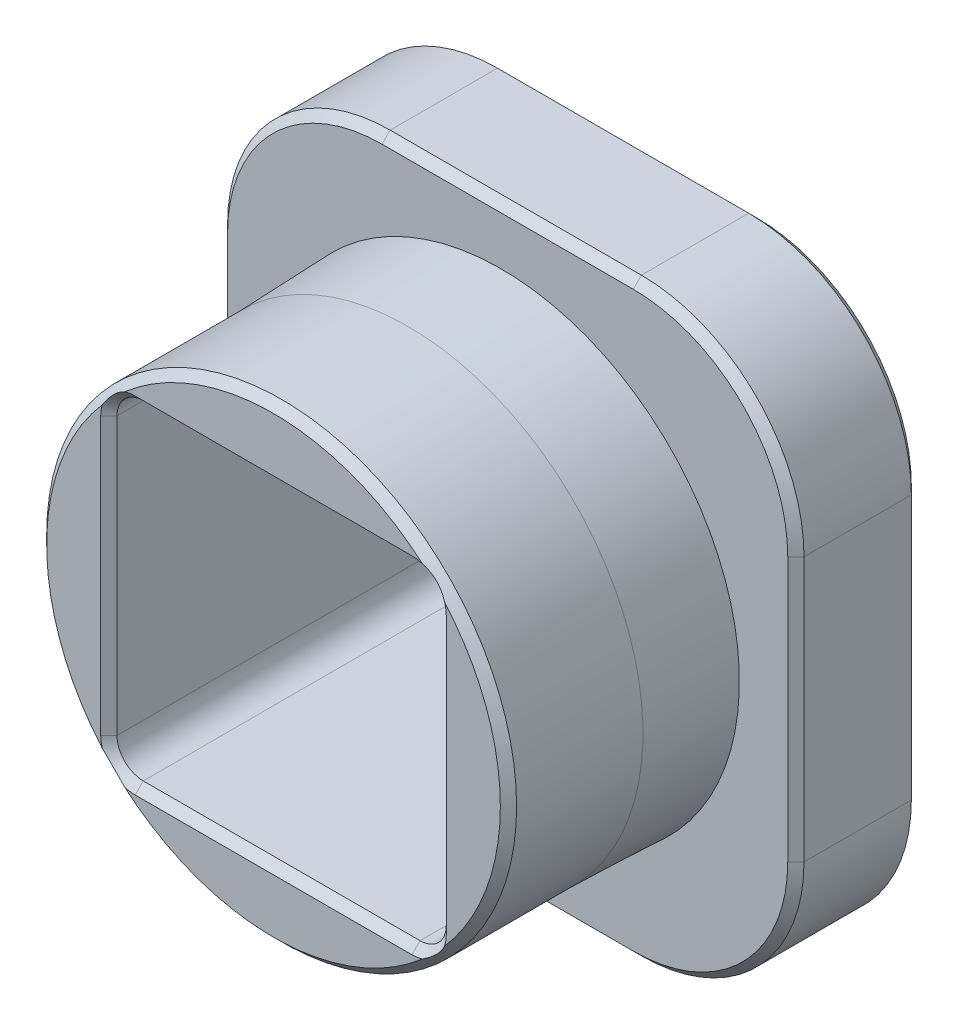
SolidWorks part; units mm, degrees
ref_plane "Front Plane (Z)" through (0, 0, 0) normal (0, 0, 1) x (1, 0, 0)
ref_plane "Top Plane (Y)" through (0, 0, 0) normal (0, 1, 0) x (1, 0, 0)
ref_plane "Side Plane (X)" through (0, 0, 0) normal (1, 0, 0) x (0, 0, -1)
sketch "Sketch1" plane through (0, 0, 0) normal (0, 0, 1) x (1, 0, 0)
  line L0 (9.652, -9.652) -> (10.3465, -8.9575) construction
  line L1 (-8.5101, -10.125) -> (8.5101, -10.125)
  line L2 (-10.125, -8.5101) -> (-10.125, 8.5101)
  line L3 (-8.5101, 10.125) -> (8.5101, 10.125)
  line L4 (10.125, -8.5101) -> (10.125, 8.5101)
  line L5 (-10.125, -10.125) -> (10.125, 10.125) construction
  line L6 (-10.125, 10.125) -> (10.125, -10.125) construction
  line L7 (-9.652, 9.652) -> (-9.1112, 10.1928) construction
  circle A0 centre (0, 0) radius 14.45
  arc A1 (8.5101, -10.125) -> (10.125, -8.5101) centre (8.5101, -8.5101) ccw
  arc A2 (-8.5101, 10.125) -> (-10.125, 8.5101) centre (-8.5101, 8.5101) ccw
  arc A3 (-8.5101, -10.125) -> (-10.125, -8.5101) centre (-8.5101, -8.5101) cw
  arc A4 (10.125, 8.5101) -> (8.5101, 10.125) centre (8.5101, 8.5101) ccw
  point P0 (0, 0)
  dimension "D2" = 28.9
  dimension "D3" = 27.3
  dimension "D1" = 20.25
extrude "Boss-Extrude1" add sketch "Sketch1" along normal blind 14
sketch "Sketch2" plane through (0, 0, 0) normal (0, 0, -1) x (-1, 0, 0)
  line L0 (10.125, 8.5101) -> (10.125, -8.5101) construction
  line L1 (-18.125, -18.125) -> (17.325, -18.125)
  line L2 (-18.125, -18.125) -> (-18.125, 18.125)
  line L3 (-18.125, 18.125) -> (17.325, 18.125)
  line L4 (18.125, -18.125) -> (18.125, 18.125) construction
  line L5 (-18.125, -18.125) -> (18.125, 18.125) construction
  line L6 (-18.125, 18.125) -> (18.125, -18.125) construction
  line L8 (17.325, 18.125) -> (17.325, -18.125)
  line L10 (8.5101, -10.125) -> (-8.5101, -10.125) construction
  line L11 (-8.5101, 10.125) -> (8.5101, 10.125) construction
  line L12 (-10.125, -8.5101) -> (-10.125, 8.5101) construction
  line L13 (8.5101, -10.125) -> (-8.5101, -10.125)
  line L14 (10.125, 8.5101) -> (10.125, -8.5101)
  line L15 (-8.5101, 10.125) -> (8.5101, 10.125)
  line L16 (-10.125, -8.5101) -> (-10.125, 8.5101)
  line L17 (17.325, 18.125) -> (18.125, 18.125) construction
  line L18 (17.325, -18.125) -> (18.125, -18.125) construction
  arc A0 (-10.125, -8.5101) -> (-8.5101, -10.125) centre (-8.5101, -8.5101) ccw construction
  arc A1 (8.5101, -10.125) -> (10.125, -8.5101) centre (8.5101, -8.5101) ccw construction
  arc A2 (10.125, 8.5101) -> (8.5101, 10.125) centre (8.5101, 8.5101) ccw construction
  arc A3 (-8.5101, 10.125) -> (-10.125, 8.5101) centre (-8.5101, 8.5101) ccw construction
  arc A4 (-10.125, -8.5101) -> (-8.5101, -10.125) centre (-8.5101, -8.5101) ccw
  arc A5 (8.5101, -10.125) -> (10.125, -8.5101) centre (8.5101, -8.5101) ccw
  arc A6 (10.125, 8.5101) -> (8.5101, 10.125) centre (8.5101, 8.5101) ccw
  arc A7 (-8.5101, 10.125) -> (-10.125, 8.5101) centre (-8.5101, 8.5101) ccw
  point P0 (0, 0)
  dimension "D1" = 8
  dimension "D2" = 7.2
extrude "Boss-Extrude2" add sketch "Sketch2" along normal blind 7.6
fillet "Fillet1" radius 10 4 edges at (18.125, -18.125, -3.8) (-17.325, -18.125, -3.8) (-17.325, 18.125, -3.8) (18.125, 18.125, -3.8)
sketch "Sketch3" plane through (-17.325, 0, 0) normal (-1, 0, 0) x (0, 0, 1)
  line L0 (0, 0) -> (-7.6, 0) construction
  line L1 (-7.6, -8.125) -> (-7.6, 8.125) construction
  circle A0 centre (-3.8, 0) radius 2.3
  dimension "D1" = 4.6
extrude "Cut-Extrude1" cut sketch "Sketch3" against normal up to next
chamfer "Chamfer1" distance 0.5 angle 45 26 edges at (0, 10.125, -7.6) (9.652, 9.652, -7.6) (10.125, 0, -7.6) (9.652, -9.652, -7.6) (0, -10.125, -7.6) (-9.652, -9.652, -7.6) (-10.125, 0, -7.6) (-9.652, 9.652, -7.6) (-17.325, 0, -7.6) (-14.3961, -15.1961, -7.6) (0.4, -18.125, -7.6) (15.1961, -15.1961, -7.6) (18.125, 0, -7.6) (18.125, 0, 0) (15.1961, -15.1961, 0) (-17.325, 0, 0) (0.4, -18.125, 0) (-14.3961, -15.1961, 0) (-17.325, -2.3, -3.8) (-10.125, 2.3, -3.8) (0.4, 18.125, -7.6) (15.1961, 15.1961, -7.6) (-14.3961, 15.1961, -7.6) (15.1961, 15.1961, 0) (0.4, 18.125, 0) (-14.3961, 15.1961, 0)
chamfer "Chamfer2" distance 0.2 angle 88 1 edges at (14.45, 0, 0) first distance on face at (0.4, 0, 0)
chamfer "Chamfer3" distance 0.5 angle 45 9 edges at (14.45, 0, 14) (0, 10.125, 14) (-9.652, 9.652, 14) (9.652, 9.652, 14) (-10.125, 0, 14) (10.125, 0, 14) (-9.652, -9.652, 14) (9.652, -9.652, 14) (0, -10.125, 14)
